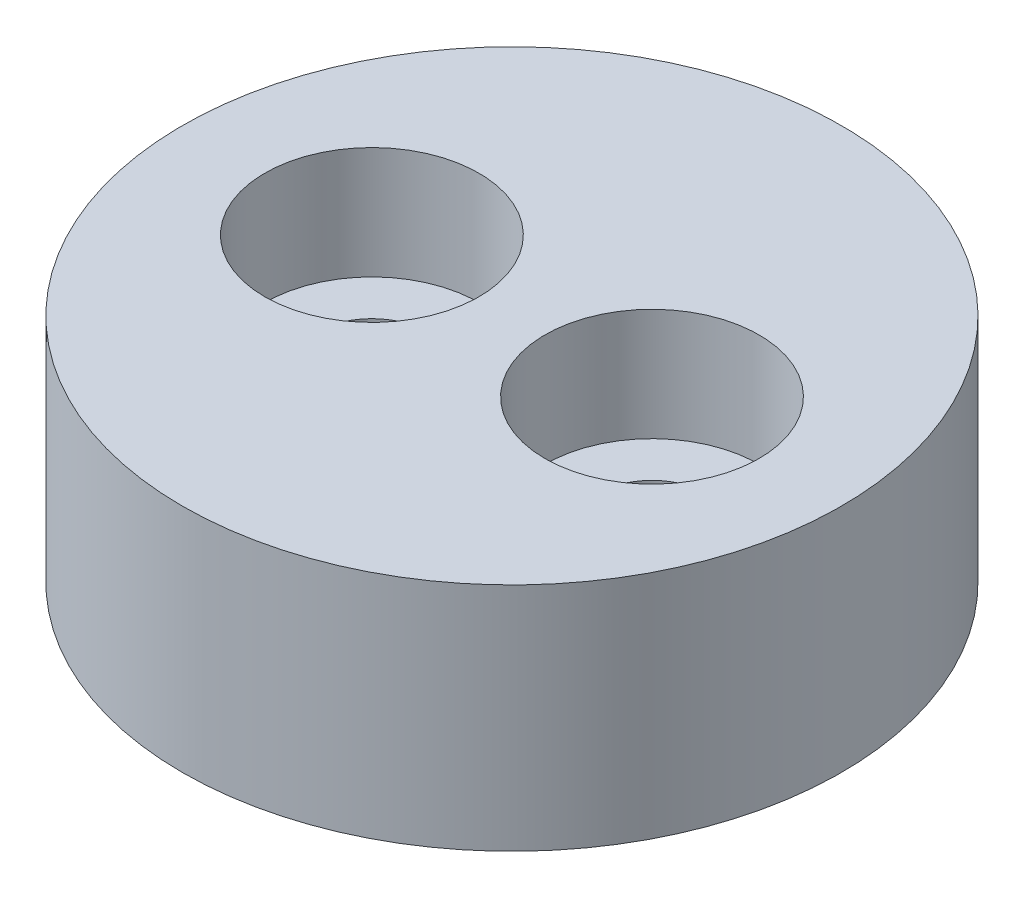
SolidWorks part; units mm, degrees
ref_plane "Ebene vorne" through (0, 0, 0) normal (0, 0, 1) x (1, 0, 0)
ref_plane "Ebene oben" through (0, 0, 0) normal (0, 1, 0) x (1, 0, 0)
ref_plane "Ebene rechts" through (0, 0, 0) normal (1, 0, 0) x (0, 0, -1)
sketch "Skizze1" plane through (0, 0, 0) normal (0, 1, 0) x (1, 0, 0)
  circle A0 centre (0, 0) radius 10
  dimension "D1" = 20
extrude "Aufsatz-Linear austragen1" add sketch "Skizze1" along normal blind 7
hole_wizard "Stirnsenkung für M3 Zylinderschraube mit Innensechskant1" positions "Skizze2" profile "Skizze3" counterbore size "M3" standard "ISO" end condition through all
sketch "Skizze2" plane through (0, 7, 0) normal (0, 1, 0) x (1, 0, 0)
  line L0 (0, 0) -> (-50000, 0) construction
  line L1 (0, 0) -> (0, -50000) construction
  point P8 (-4.25, 0)
  point P10 (4.25, 0)
  dimension "D1" = 8.5
sketch "Skizze3" plane through (4.25, 7, 0) normal (1, 0, 0) x (0, 0, 1)
  line L0 (0, 0) -> (0, 7)
  line L1 (0, 7) -> (1.7, 7)
  line L3 (1.7, 7) -> (1.7, 3.4)
  line L4 (1.7, 3.4) -> (3.25, 3.4)
  line L5 (3.25, 3.4) -> (3.25, 0)
  line L7 (3.25, 0) -> (0, 0)
  line L11 (0, -6.35) -> (0, 107.95) construction
  dimension "Bohrerdurchmesser" = 3.4
  dimension "Bohrungstiefe" = 7
  dimension "Senkdurchmesser2" = 6.5
  dimension "Senktiefe2" = 3.4
